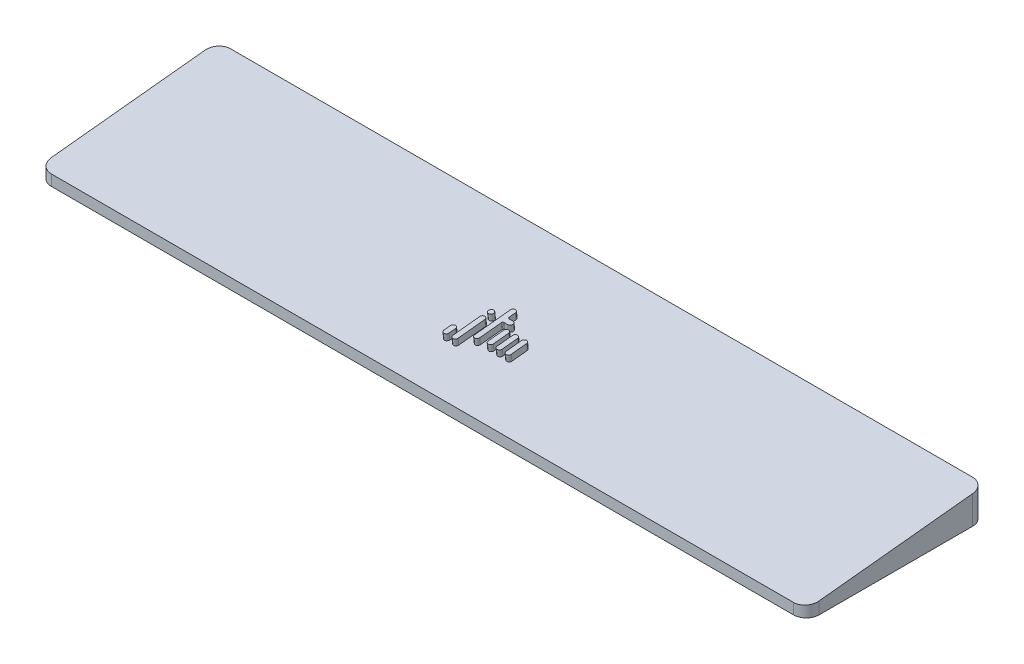
SolidWorks part; units mm, degrees
material "Brass"
ref_plane "Front Plane" through (0, 0, 0) normal (0, 0, 1) x (1, 0, 0)
ref_plane "Top Plane" through (0, 0, 0) normal (0, 1, 0) x (1, 0, 0)
ref_plane "Right Plane" through (0, 0, 0) normal (1, 0, 0) x (0, 0, -1)
sketch "Sketch1" plane through (0, 0, 0) normal (0, 1, 0) x (1, 0, 0)
  line L1 (0, 0) -> (300, 0)
  line L2 (0, 0) -> (0, 70)
  line L3 (0, 70) -> (300, 70)
  line L4 (300, 0) -> (300, 70)
  dimension "D1" = 300
  dimension "D2" = 70
ref_plane "Plane1" through (0, 0, 0) normal (0, 0.9945, 0.1045) x (1, 0, 0)
ref_plane "Plane2" through (0, 4.177, 0.439) normal (0, 0.9945, 0.1045) x (1, 0, 0)
extrude "Boss-Extrude1" add sketch "Sketch1" along normal up to surface (4.2231 mm away) contours L3 L4 L1 L2 up to plane "Plane2"
sketch "Sketch2" plane through (0, 4.177, 0.439) normal (0, 0.9945, 0.1045) x (-1, 0, 0)
  line L0 (-147.1, -31.1414) -> (-149.1, -31.1414) construction
  line L1 (-147.1, -39.1414) -> (-149.1, -39.1414)
  line L2 (-147.1, -39.1414) -> (-147.1, -23.1414)
  line L3 (-147.1, -23.1414) -> (-149.1, -23.1414)
  line L4 (-149.1, -39.1414) -> (-149.1, -23.1414)
  line L5 (-142.6, -31.6414) -> (-144.6, -31.6414)
  line L6 (-142.6, -31.6414) -> (-142.6, -19.1414)
  line L7 (-142.6, -19.1414) -> (-144.6, -19.1414)
  line L8 (-144.6, -31.6414) -> (-144.6, -19.1414)
  line L9 (-151.9, -31.6414) -> (-153.9, -31.6414)
  line L10 (-151.9, -31.6414) -> (-151.9, -23.6414)
  line L11 (-151.9, -23.6414) -> (-153.9, -23.6414)
  line L12 (-153.9, -31.6414) -> (-153.9, -23.6414)
  line L13 (-155.4, -31.6414) -> (-157.4, -31.6414)
  line L14 (-155.4, -31.6414) -> (-155.4, -23.6414)
  line L15 (-155.4, -23.6414) -> (-157.4, -23.6414)
  line L16 (-157.4, -31.6414) -> (-157.4, -23.6414)
  line L17 (-158.9, -31.6414) -> (-160.9, -31.6414)
  line L18 (-158.9, -31.6414) -> (-158.9, -23.6414)
  line L19 (-158.9, -23.6414) -> (-160.9, -23.6414)
  line L20 (-160.9, -31.6414) -> (-160.9, -23.6414)
  line L25 (-142.6, -31.6414) -> (-157.4, -31.6414) construction
  line L27 (-151.1, -35.1414) -> (-147.1, -35.1414)
  line L28 (-151.1, -33.1414) -> (-147.1, -33.1414)
  line L30 (0, -0.4414) -> (0, -70.827) construction
  line L31 (-139.1, -23.6414) -> (-141.1, -23.6414)
  line L32 (-139.1, -23.6414) -> (-139.1, -19.1414)
  line L33 (-139.1, -19.1414) -> (-141.1, -19.1414)
  line L34 (-141.1, -23.6414) -> (-141.1, -19.1414)
  line L35 (0, -0.4414) -> (-300, -0.4414) construction
  circle A0 centre (-143.6, -34.1414) radius 1
  circle A2 centre (-151.1, -34.1414) radius 1
  circle A3 centre (-148.1, -38.1414) radius 1
  circle A4 centre (-148.1, -24.1414) radius 1
  circle A5 centre (-143.6, -30.6414) radius 1
  circle A6 centre (-143.6, -20.1414) radius 1
  circle A7 centre (-140.1, -22.6414) radius 1
  circle A8 centre (-140.1, -20.1414) radius 1
  circle A9 centre (-152.9, -30.6414) radius 1
  circle A10 centre (-152.9, -24.6414) radius 1
  circle A11 centre (-156.4, -30.6414) radius 1
  circle A12 centre (-156.4, -24.6414) radius 1
  circle A13 centre (-159.9, -30.6414) radius 1
  circle A14 centre (-159.9, -24.6414) radius 1
  point P29 (-143.6, -31.6414)
  point P32 (-143.6, -19.1414)
  point P44 (-148.1, -39.1414)
  dimension "D12" = 2
  dimension "D13" = 12.5
  dimension "D16" = 2
  dimension "D1" = 16
  dimension "D2" = 2
  dimension "D3" = 0
  dimension "D4" = 2.5
  dimension "D5" = 2.8
  dimension "D6" = 1.5
  dimension "D7" = 1.5
  dimension "D8" = 8
  dimension "D9" = 0.5
  dimension "D10" = 1.5
  dimension "D11" = 2.5
  dimension "D14" = 4.5
  dimension "D15" = 147.1
  dimension "D17" = 2
  dimension "D18" = 3
  dimension "D19" = 11
  dimension "D20" = 18.7
extrude "Boss-Extrude2" add sketch "Sketch2" along normal blind 2.5 contours A7 | A8 L34 A7 L32 | A8 | A6 | A6 L8 A5 L6 | A5 | A0 | A3 | A3 L2 L27 L4 | L28 L4 L27 L2 | A4 L4 L28 L2 | A4 | A2 | A2 L27 L4 L28 | A9 | A10 L12 A9 L10 | A10 | A11 | A12 | A13 | A14 | A12 L16 A11 L14 | A14 L20 A13 L18 region at (148.1, 8.1639, -37.4935) region at (148.1, 7.9672, -35.6223) region at (148.1, 7.7457, -33.5154) region at (149.7278, 7.7457, -33.5154) region at (148.1, 7.2116, -28.433) region at (151.1, 7.7457, -33.5154) region at (148.1, 6.7005, -23.5702) region at (143.6, 7.3799, -30.0346) region at (143.6, 6.8311, -24.8133) region at (143.6, 6.2823, -19.5921) region at (152.9, 7.3799, -30.0346) region at (152.9, 7.0663, -27.051) region at (152.9, 6.7527, -24.0674) region at (156.4, 7.3799, -30.0346) region at (156.4, 7.0663, -27.051) region at (156.4, 6.7527, -24.0674) region at (159.9, 7.3799, -30.0346) region at (159.9, 7.0663, -27.051) region at (159.9, 6.7527, -24.0674) region at (140.1, 6.5437, -22.0784) region at (140.1, 6.413, -20.8352) region at (140.1, 6.2823, -19.5921) region at (143.6, 7.7457, -33.5154)
fillet "Fillet1" radius 5 4 edges at (300, 5.7902, -70) (300, 2.1116, 0) (0, 2.1116, 0) (0, 5.7902, -70)
fillet "Fillet2" radius 0.5 2 edges at (149.1, 9.0934, -34.3792) (149.1, 8.8844, -32.3902)
